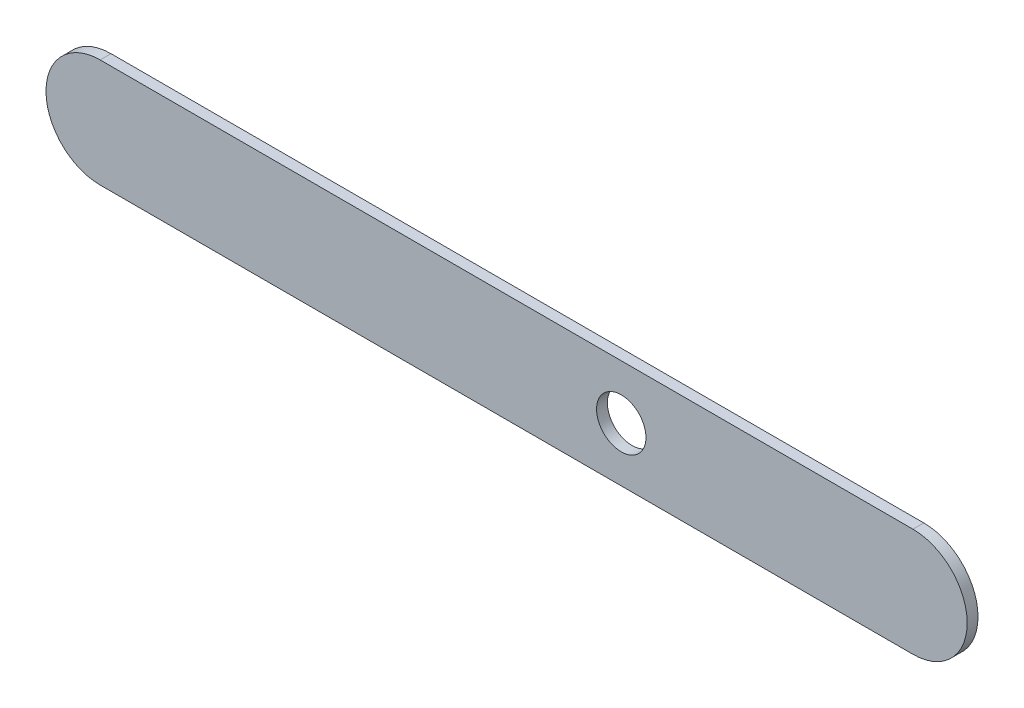
SolidWorks part; units mm, degrees
ref_plane "Front Plane" through (0, 0, 0) normal (0, 0, 1) x (1, 0, 0)
ref_plane "Top Plane" through (0, 0, 0) normal (0, 1, 0) x (1, 0, 0)
ref_plane "Right Plane" through (0, 0, 0) normal (1, 0, 0) x (0, 0, -1)
sketch "Sketch1" plane through (0, 0, 0) normal (0, 0, 1) x (1, 0, 0)
  line L0 (0, 0) -> (150, 0) construction
  line L1 (0, 10) -> (150, 10)
  line L2 (0, -10) -> (150, -10)
  arc A0 (0, 10) -> (0, -10) centre (0, 0) ccw
  arc A1 (150, -10) -> (150, 10) centre (150, 0) ccw
  circle A2 centre (96.159, 0) radius 4.5581
  point P3 (75, 0)
  dimension "D1" = 10
  dimension "D2" = 150
extrude "Boss-Extrude1" add sketch "Sketch1" along normal mid plane 2
